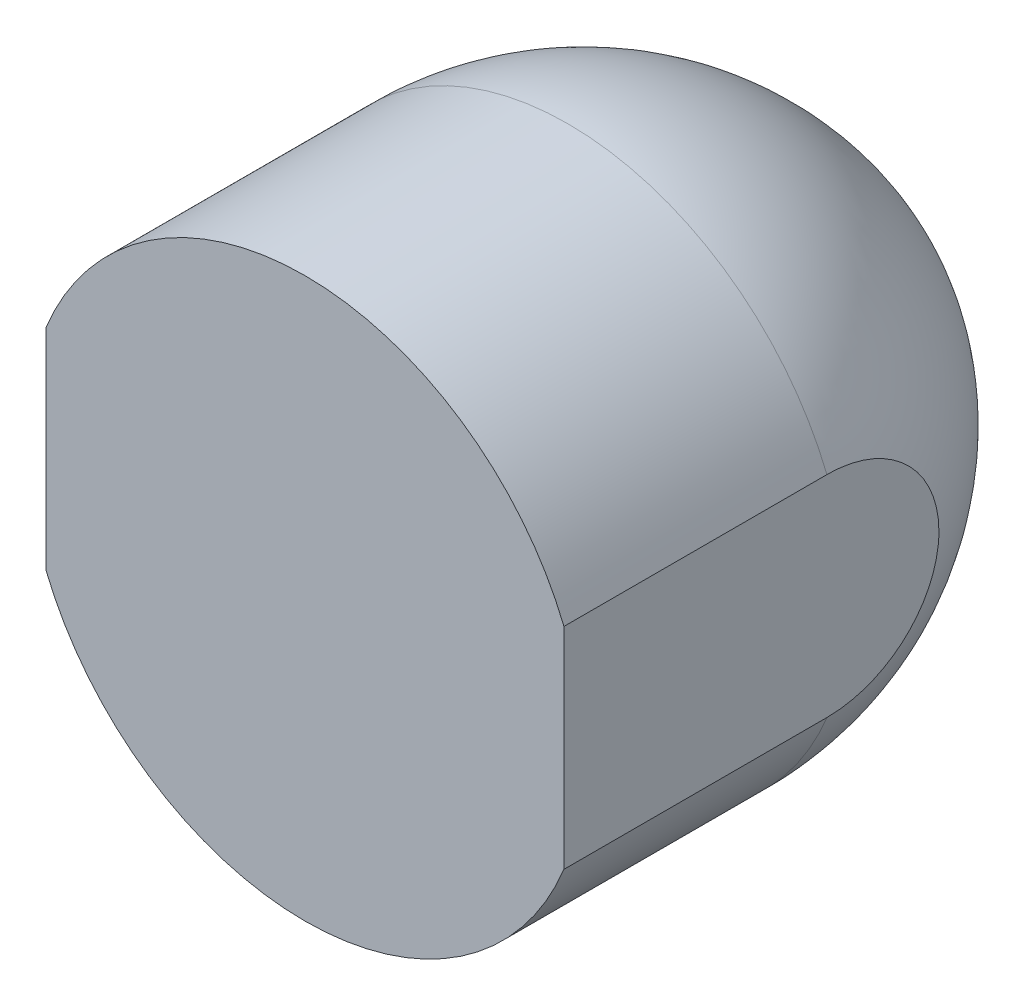
SolidWorks part; units mm, degrees
ref_plane "Front Plane" through (0, 0, 0) normal (0, 0, 1) x (1, 0, 0)
ref_plane "Top Plane" through (0, 0, 0) normal (0, 1, 0) x (1, 0, 0)
ref_plane "Right Plane" through (0, 0, 0) normal (1, 0, 0) x (0, 0, -1)
sketch "Sketch1" plane through (0, 0, 0) normal (0, 1, 0) x (1, 0, 0)
  line L0 (0, 0) -> (5.315, 0)
  line L1 (5.315, 0) -> (5.315, 5)
  line L2 (0, 0) -> (0, 10.9608)
  arc A1 (5.315, 5) -> (0, 10.9608) centre (-0.685, 5) ccw
  point P2 (0, 0)
  point P7 (0, 0)
  dimension "D1" = 5.315
  dimension "D2" = 5
  dimension "D3" = 6
revolve "Revolve2" add sketch "Sketch1" angle 360 about L2
sketch "Sketch3" plane through (0, 0, 0) normal (0, 0, 1) x (1, 0, 0)
  line L0 (-4.9244, -2) -> (-4.9244, 2)
  circle A0 centre (0, 0) radius 5.315 construction
  dimension "D1" = 4
extrude "Cut-Extrude2" cut sketch "Sketch3" against normal through all and the other way through all
sketch "Sketch4" plane through (0, 0, 0) normal (0, 0, 1) x (1, 0, 0)
  line L0 (4.9244, -2) -> (4.9244, 2)
  arc A0 (-4.9244, -2) -> (-4.9244, 2) centre (0, 0) ccw construction
  dimension "D1" = 4
extrude "Cut-Extrude4" cut sketch "Sketch4" against normal through all and the other way through all flip side to cut
